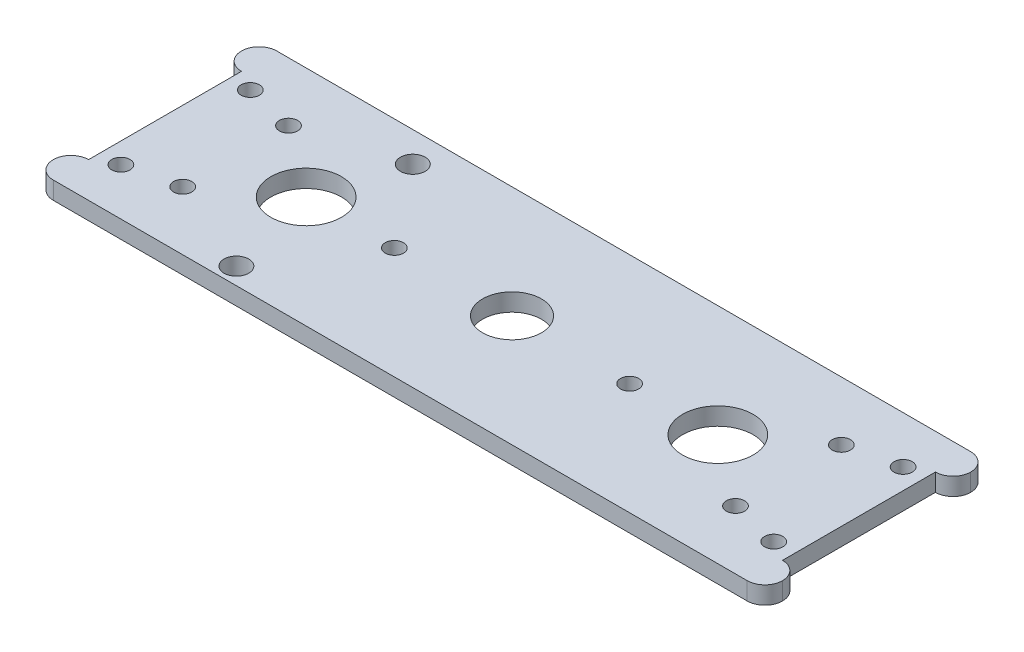
SolidWorks part; units mm, degrees
material "Thornel Mat VMA"
ref_plane "Front Plane" through (0, 0, 0) normal (0, 0, 1) x (1, 0, 0)
ref_plane "Top Plane" through (0, 0, 0) normal (0, 1, 0) x (1, 0, 0)
ref_plane "Right Plane" through (0, 0, 0) normal (1, 0, 0) x (0, 0, -1)
sketch "Sketch1" plane through (0, 0, 0) normal (0, 1, 0) x (1, 0, 0)
  line L0 (0, 0) -> (0, 56.5511) construction
  line L1 (0, 0) -> (118.6796, 0) construction
  line L2 (-62, 19) -> (62, 19)
  line L5 (-62, -19) -> (62, -19)
  line L6 (62, 19) -> (62, 13)
  line L7 (62, 13) -> (59, 13)
  line L8 (59, 13) -> (59, -13)
  line L9 (62, -13) -> (59, -13)
  line L10 (62, -19) -> (62, -13)
  line L11 (-62, -19) -> (-62, -13)
  line L12 (-62, -13) -> (-59, -13)
  line L13 (-59, 13) -> (-59, -13)
  line L14 (-62, 13) -> (-59, 13)
  line L15 (-62, 19) -> (-62, 13)
  circle A0 centre (55.5, 11) radius 1.55
  circle A1 centre (-55.5, 11) radius 1.55
  circle A2 centre (-55.5, -11) radius 1.55
  circle A3 centre (55.5, -11) radius 1.55
  circle A4 centre (0, 0) radius 5
  circle A5 centre (20, 0) radius 1.55
  circle A6 centre (-20, 0) radius 1.55
  circle A7 centre (35, 0) radius 6
  circle A8 centre (-35, 0) radius 6
  circle A9 centre (47, 9) radius 1.55
  circle A10 centre (47, -9) radius 1.55
  circle A11 centre (-47, -9) radius 1.55
  circle A12 centre (-47, 9) radius 1.55
  point P13 (0, 19)
  point P18 (-61, 0)
  point P19 (61, 0)
  point P28 (59, 0)
  dimension "D1" = 3.1
  dimension "D2" = 3.5
  dimension "D3" = 8
  dimension "D4" = 3.1
  dimension "D5" = 10
  dimension "D6" = 20
  dimension "D11" = 35
  dimension "D12" = 12
  dimension "D13" = 8.5
  dimension "D14" = 2
  dimension "D7" = 38
  dimension "D8" = 124
  dimension "D9" = 3
  dimension "D10" = 6
extrude "Boss-Extrude1" add sketch "Sketch1" along normal blind 3
fillet "Fillet1" radius 3 8 edges at (-62, 1.5, -19) (-62, 1.5, -13) (-62, 1.5, 13) (-62, 1.5, 19) (62, 1.5, 19) (62, 1.5, 13) (62, 1.5, -13) (62, 1.5, -19)
sketch "草图2" plane through (0, 3, 0) normal (0, 1, 0) x (1, 0, 0)
  line L0 (0, 19) -> (0, -19) construction
  line L1 (59, 19) -> (-59, 19) construction
  line L2 (-59, -19) -> (59, -19) construction
  line L3 (0, 0) -> (-21.55, 0) construction
  circle A0 centre (-20, 0) radius 1.55 construction
sketch "草图3" plane through (0, 0, 0) normal (0, -1, 0) x (1, 0, 0)
  circle A0 centre (-30.7485, -13.885) radius 2.1 construction
  circle A1 centre (-30.7485, -13.885) radius 2.1
  circle A2 centre (-30.7485, 16.115) radius 2.1 construction
  circle A3 centre (-30.7485, 16.115) radius 2.1
extrude "切除-拉伸1" cut sketch "草图3" against normal blind 10
